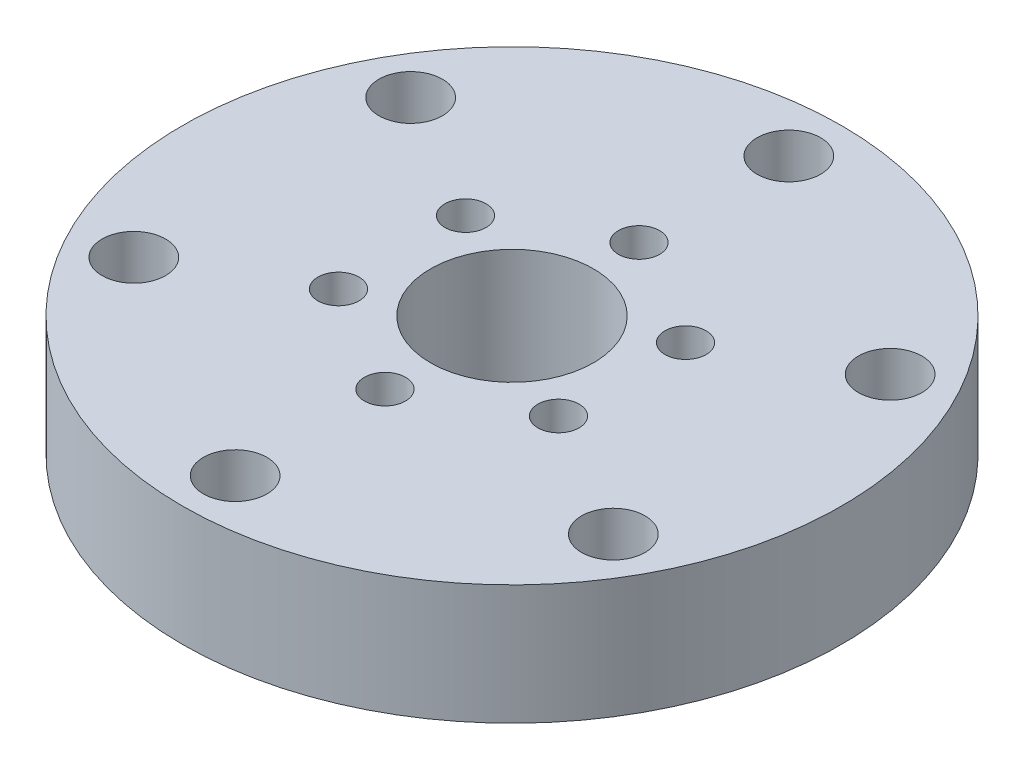
SolidWorks part; units mm, degrees
ref_plane "Front Plane" through (0, 0, 0) normal (0, 0, 1) x (1, 0, 0)
ref_plane "Top Plane" through (0, 0, 0) normal (0, 1, 0) x (1, 0, 0)
ref_plane "Right Plane" through (0, 0, 0) normal (1, 0, 0) x (0, 0, -1)
sketch "Sketch1" plane through (0, 0, 0) normal (0, 1, 0) x (1, 0, 0)
  circle A0 centre (0, 0) radius 34.925
  dimension "D1" = 69.85
extrude "Extrude1" add sketch "Sketch1" along normal blind 12.7
sketch "Sketch2" plane through (0, 0, 0) normal (0, 1, 0) x (1, 0, 0)
  circle A0 centre (0, 0) radius 8.636
  dimension "D1" = 17.272
extrude "Cut-Extrude1" cut sketch "Sketch2" along normal through all
sketch "Sketch3" plane through (0, 0, 0) normal (0, 1, 0) x (1, 0, 0)
  circle A0 centre (0, 29.337) radius 3.3655
  dimension "D1" = 6.731
  dimension "D2" = 29.337
extrude "Cut-Extrude2" cut sketch "Sketch3" along normal blind 12.7
ref_axis "Axis1" through (0, 35.8582, 0) along (0, -1, 0)
pattern_circular "CirPattern1" count 6 over 360 about axis through (0, 35.8582, 0) along (0, -1, 0) of "Cut-Extrude2"
sketch "Sketch4" plane through (0, 0, 0) normal (0, 1, 0) x (1, 0, 0)
  line L0 (0, 0) -> (0, 16.8619)
sketch "Sketch5" plane through (0, 0, 0) normal (0, 1, 0) x (1, 0, 0)
  circle A0 centre (0, 13.462) radius 2.1844
  dimension "D1" = 4.3688
extrude "Cut-Extrude4" cut sketch "Sketch5" along normal through all
pattern_circular "CirPattern2" count 6 over 360 about axis through (0, 35.8582, 0) along (0, -1, 0) of "Cut-Extrude4"
